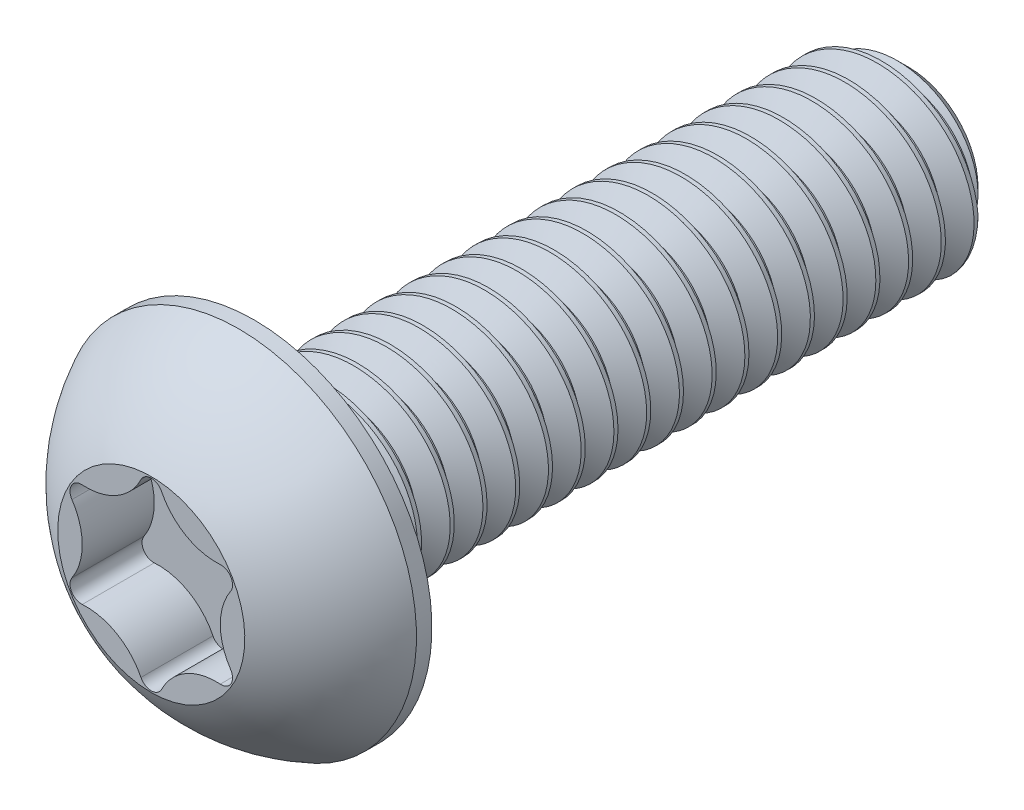
SolidWorks part; units mm, degrees
material "Plain Carbon Steel"
ref_plane "Front" through (0, 0, 0) normal (0, 0, 1) x (1, 0, 0)
ref_plane "Top" through (0, 0, 0) normal (0, 1, 0) x (1, 0, 0)
ref_plane "Right" through (0, 0, 0) normal (1, 0, 0) x (0, 0, -1)
sketch "Sketch1" plane through (0, 0, 0) normal (1, 0, 0) x (0, 0, -1)
  line L2 (-7, 2) -> (7, 2)
  line L3 (7, 2) -> (7, 0)
  line L4 (7, 0) -> (-7, 0)
  line L6 (-7.33, 3.8) -> (-7, 3.8) construction
  line L7 (7, 2) -> (7, -2) construction
  line L8 (-9.2, 0) -> (-7, 0) construction
  line L9 (-7, 3.8) -> (-7, -3.8) construction
  line L11 (-7, 2) -> (-7, 0)
  line L14 (-9.2, 0) -> (-9.2, 2) construction
  line L15 (7, -2) -> (6.3, -2) construction
  arc A3 (-9.2, 2) -> (-7.33, 3.8) centre (-5.4736, 0) cw construction
  point P10 (5.95, -2)
  point P15 (0, 0)
  dimension "Thread OD" = 4
  dimension "D1" = 0.33
  dimension "Head Height" = 2.2
  dimension "Head Diameter" = 7.6
  dimension "Length" = 14
  dimension "Thread Pitch" = 0.7
  dimension "D2" = 1.05
sketch "Sketch2" plane through (0, 0, 0) normal (0, 0, 1) x (1, 0, 0)
  line L0 (0, 0) -> (-1.7048, 0.9843)
  line L1 (0, 0) -> (-1.7048, -0.9842)
  line L2 (0, 1.9685) -> (0, 1.7224) construction
  line L3 (0, 1.7224) -> (0, 1.4764) construction
  circle A0 centre (0, 0) radius 1.9685 construction
  circle A1 centre (0, 0) radius 1.4764 construction
  circle A2 centre (0, 0) radius 1.7224 construction
  arc A4 (-1.6962, 0.7245) -> (-1.6962, -0.7245) centre (-2.7799, 0) cw
  arc A5 (-1.6962, 0.7245) -> (-1.7048, 0.9843) centre (-1.4917, 0.8612) cw
  arc A6 (-1.6962, -0.7245) -> (-1.7048, -0.9842) centre (-1.4917, -0.8612) ccw
  point P3 (0, -1.9685)
  dimension "Torx OD" = 3.937
  dimension "D1" = 2.9527
  dimension "D2" = 60
sketch "Sketch12" plane through (0, 0, 0) normal (1, 0, 0) x (0, 0, -1)
  line L0 (-7, 2) -> (-7, 0) construction
  line L1 (7, 0) -> (-7, 0) construction
  line L2 (7, 2) -> (7, 0) construction
  line L3 (-7, 2) -> (7, 2) construction
  line L4 (-7, 2) -> (-7, 0)
  line L5 (7, 0) -> (-7, 0)
  line L6 (7, 2) -> (7, 0)
  line L7 (-7, 2) -> (7, 2)
revolve "Revolve1" add sketch "Sketch12" angle 360 about L5
sketch "Sketch7" plane through (0, 0, 0) normal (1, 0, 0) x (0, 0, -1)
  line L0 (-9.2, 0) -> (-9.2, 2) construction
  line L6 (-7.33, 3.8) -> (-7, 3.8) construction
  line L8 (-9.2, 0) -> (-7, 0) construction
  line L11 (-7, 3.8) -> (-7, -3.8) construction
  line L12 (-7.33, 3.8) -> (-7, 3.8)
  line L13 (-9.2, 0) -> (-7, 0)
  line L15 (-7, 3.8) -> (-7, 0)
  line L16 (-9.2, 2) -> (-9.2, 0)
  arc A2 (-7.33, 3.8) -> (-9.2, 2) centre (-5.4736, 0) ccw construction
  arc A3 (-7.33, 3.8) -> (-9.2, 2) centre (-5.4736, 0) ccw
revolve "Revolve2" add sketch "Sketch7" angle 360 mid plane about L13
sketch "Sketch11" plane through (0, 0, 9.2) normal (0, 0, 1) x (1, 0, 0)
  line L0 (0, 0) -> (-1.7048, 0.9843) construction
  line L1 (0, 0) -> (-1.7048, -0.9843) construction
  line L2 (0, 0) -> (-1.7048, 0.9843)
  line L3 (0, 0) -> (-1.7048, -0.9843)
  arc A0 (-1.7048, 0.9843) -> (-1.6962, 0.7245) centre (-1.4917, 0.8612) ccw construction
  arc A1 (-1.6962, -0.7245) -> (-1.6962, 0.7245) centre (-2.7799, 0) ccw construction
  arc A3 (-1.6962, -0.7245) -> (-1.7048, -0.9843) centre (-1.4917, -0.8612) ccw construction
  arc A4 (-1.7048, 0.9843) -> (-1.6962, 0.7245) centre (-1.4917, 0.8612) ccw
  arc A5 (-1.6962, -0.7245) -> (-1.6962, 0.7245) centre (-2.7799, 0) ccw
  arc A7 (-1.6962, -0.7245) -> (-1.7048, -0.9843) centre (-1.4917, -0.8612) ccw
extrude "Cut-Extrude4" cut sketch "Sketch11" against normal blind 1.54
pattern_circular "CirPattern1" count 6 over 360 of "Cut-Extrude4"
chamfer "Chamfer1" distance 0.525 angle 45 1 edges at (0, 2, -7)
split "Split1" bodies to split 122 113 resulting bodies 125 126 split by face at (0, -2, 7)
sketch "Sketch13" plane through (0, 0, -7) normal (0, 0, -1) x (-1, 0, 0)
  circle A0 centre (0, 0) radius 2 construction
  circle A1 centre (0, 0) radius 2
curve "Helix/Spiral1" pitch 0.7 height 14.7 radius 2 centre (0, 0, -7) axis (0, 0, 1) start towards (0, 1, 0)
sketch "Sketch14" plane through (0, 0, 0) normal (1, 0, 0) x (0, 0, -1)
  line L0 (7.6562, 2.0758) -> (6.9563, 2.0758) construction
  line L1 (6.9563, 2.0758) -> (7.3063, 1.4696) construction
  line L2 (7.3063, 1.4696) -> (7.6562, 2.0758) construction
  line L3 (7.6125, 2) -> (7, 2) construction
  line L4 (7.3063, 2.0758) -> (7.3063, 2) construction
  line L5 (7.6344, 2.0379) -> (6.9781, 2.0379) construction
  line L6 (7.35, 1.5453) -> (7.2625, 1.5453) construction
  line L7 (7.3063, 1.5453) -> (7.3063, 1.4696) construction
  line L8 (7.2625, 1.5453) -> (6.9781, 2.0379)
  line L9 (6.9781, 2.0379) -> (7.6344, 2.0379)
  line L10 (7.6344, 2.0379) -> (7.35, 1.5453)
  line L11 (7.35, 1.5453) -> (7.2625, 1.5453)
  point P11 (7.3063, 2.0379)
  dimension "D1" = 0.7
  dimension "D2" = 0.0875
sweep "Cut-Sweep1" cut profiles "Sketch14" path "Helix/Spiral1" align with end faces yes
combine bodies "Combine1" operation type add bodies to combine 125 127
equation "\"D3@Helix/Spiral1\" = \"Length@Sketch1\" + \"Thread Pitch@Sketch1\""
equation "\"D1@Chamfer1\"=\"D4@Helix/Spiral1\" * .75"
equation "\"D1@Sketch1\" = \"Head Height@Sketch1\" * .15"
equation "\"D1@Cut-Extrude4\" = \"Head Height@Sketch1\" * .7"
equation "\"D2@Sketch1\"=\"Thread Pitch@Sketch1\"*1.5"
equation "\"D1@Sketch14\"=\"Thread Pitch@Sketch1\""
equation "\"D2@Sketch14\"=\"D1@Sketch14\"/ 1/8"
equation "\"D4@Helix/Spiral1\"=\"Thread Pitch@Sketch1\""
equation "\"D1@Sketch2\"=\"Torx OD@Sketch2\"*.75"
